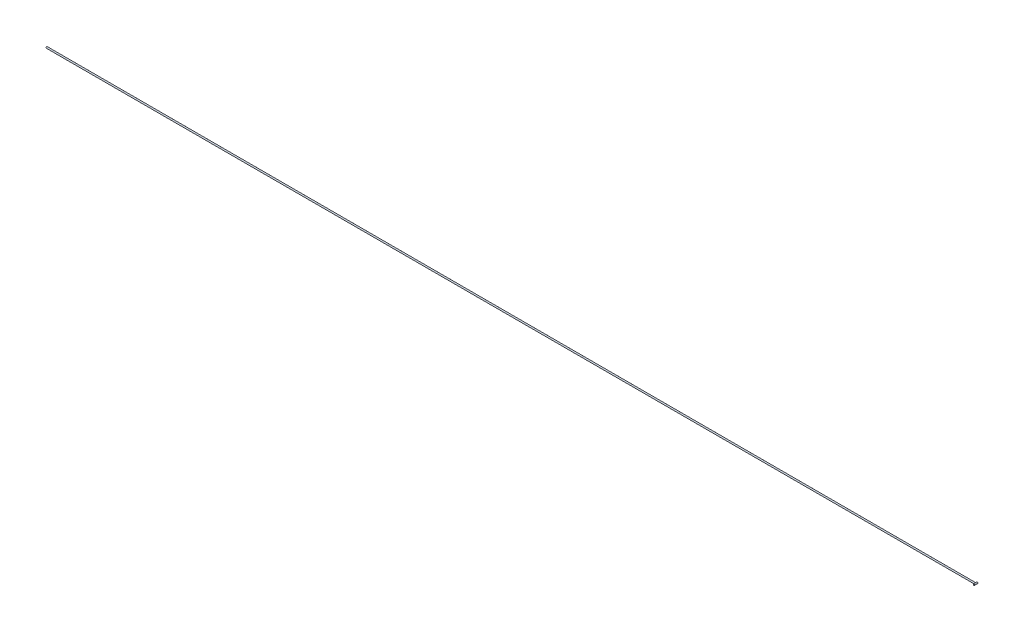
SolidWorks part; units mm, degrees
ref_plane "Plan de face" through (0, 0, 0) normal (0, 0, 1) x (1, 0, 0)
ref_plane "Plan de dessus" through (0, 0, 0) normal (0, 1, 0) x (1, 0, 0)
ref_plane "Plan de droite" through (0, 0, 0) normal (1, 0, 0) x (0, 0, -1)
sketch "Esquisse1" plane through (0, 0, 0) normal (0, 0, 1) x (1, 0, 0)
  line L0 (-687.5, 0) -> (687.5, 0)
  dimension "D1" = 1375
sweep "Balayage1" add path "Esquisse1" circular profile diameter 2 parameters "D3"=2
sketch "Esquisse16" plane through (687.5, 0, 0) normal (1, 0, 0) x (0, 0, -1)
  line L0 (-2.5, 0) -> (2.5, 0)
  dimension "D1" = 5
sweep "Balayage2" add path "Esquisse16" circular profile diameter 2 parameters "D3"=2
